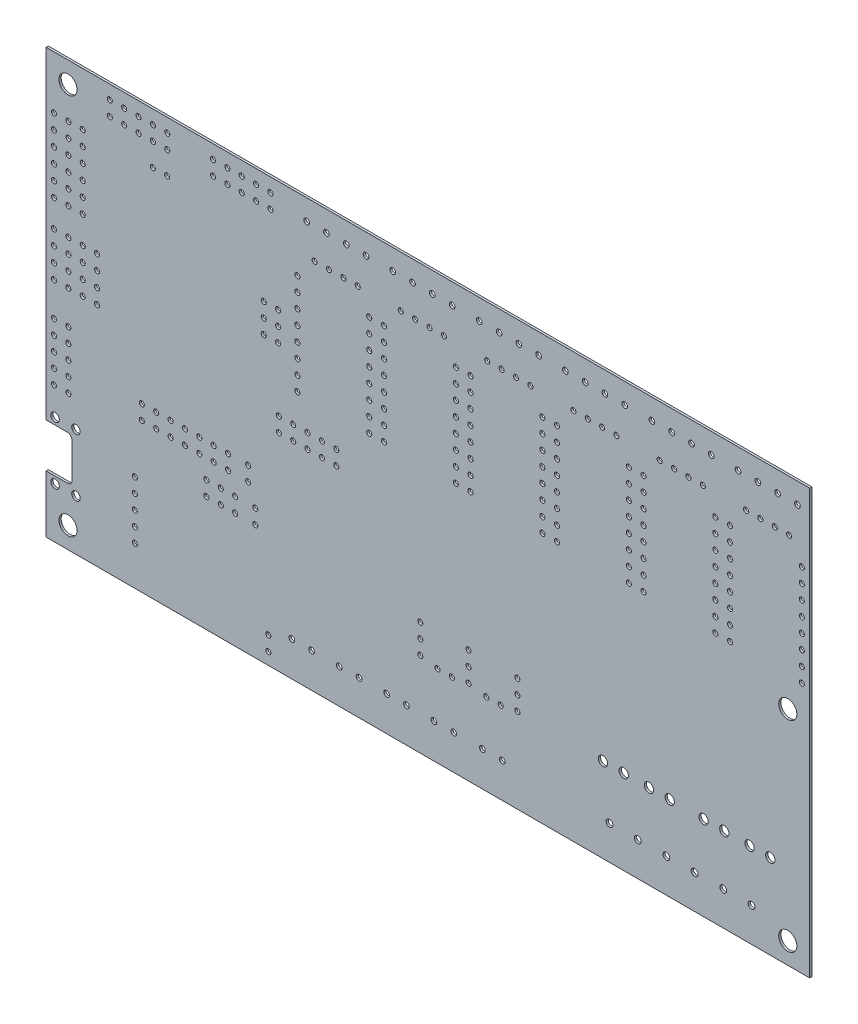
SolidWorks part; units mm, degrees
note: '?' marks a value the reader was unsure of.
ref_plane "Front Plane" through (0, 0, 0) normal (0, 0, 1) x (1, 0, 0)
ref_plane "Top Plane" through (0, 0, 0) normal (0, 1, 0) x (1, 0, 0)
ref_plane "Right Plane" through (0, 0, 0) normal (1, 0, 0) x (0, 0, -1)
ref_axis "x axis" through (-6.75, 0, 0) along (1, 0, 0)?
ref_axis "y axis" through (0, 78.75, 0) along (0, -1, 0)?
ref_axis "z axis" through (0, 0, -0.4107) along (0, 0, 1)?
sketch "Sketch1" plane through (0, 0, 0) normal (0, 0, 1) x (1, 0, 0)
  line L4 (135, 75) -> (0, 75)
  line L5 (0, 75) -> (0, 0)
  line L6 (0, 0) -> (135, 0)
  line L7 (135, 0) -> (135, 75)
extrude "Board" add sketch "Sketch1" along normal blind 0.3912
sketch "Sketch2" plane through (0, 0, 0.3912) normal (0, 0, 1) x (1, 0, 0)
  circle A0 centre (131.125, 39.25) radius 1.6
extrude "Cut-Extrude1" cut sketch "Sketch2" against normal blind 0.3912
sketch "Sketch3" plane through (0, 0, 0.3912) normal (0, 0, 1) x (1, 0, 0)
  circle A0 centre (131.125, 3.75) radius 1.6
extrude "Cut-Extrude2" cut sketch "Sketch3" against normal through all
sketch "Sketch4" plane through (0, 0, 0.3912) normal (0, 0, 1) x (1, 0, 0)
  circle A0 centre (3.875, 3.75) radius 1.6
extrude "Cut-Extrude3" cut sketch "Sketch4" against normal through all
sketch "Sketch5" plane through (0, 0, 0.3912) normal (0, 0, 1) x (1, 0, 0)
  circle A0 centre (3.875, 71.25) radius 1.6
extrude "Cut-Extrude4" cut sketch "Sketch5" against normal through all
sketch "Sketch6" plane through (0, 0, 0.3912) normal (0, 0, 1) x (1, 0, 0)
  line L0 (3.7788, 10.1428) -> (-0.0178, 10.1428)
  line L1 (-0.0178, 10.1428) -> (-0.0178, 17.9428)
  line L2 (-0.0178, 17.9428) -> (3.7788, 17.9428)
  line L3 (4.5788, 17.1428) -> (4.5788, 10.9428)
  arc A0 (3.7788, 17.9428) -> (4.5788, 17.1428) centre (3.7788, 17.1428) cw
  arc A1 (4.5788, 10.9428) -> (3.7788, 10.1428) centre (3.7787, 10.9428) cw
extrude "Cutout - Cutout 1" cut sketch "Sketch6" against normal blind 0.3912
sketch "Sketch7" plane through (0, 0, 0.3912) normal (0, 0, 1) x (1, 0, 0)
  circle A0 centre (87.0811, 71.3713) radius 0.5
  circle A1 centre (83.581, 71.3713) radius 0.5
  circle A2 centre (80.0811, 71.3713) radius 0.5
  circle A3 centre (76.5811, 71.3713) radius 0.5
  circle A4 centre (71.7826, 71.3713) radius 0.5
  circle A5 centre (68.2825, 71.3713) radius 0.5
  circle A6 centre (64.7826, 71.3713) radius 0.5
  circle A7 centre (61.2826, 71.3713) radius 0.5
  circle A8 centre (56.5639, 71.3713) radius 0.5
  circle A9 centre (53.0639, 71.3713) radius 0.5
  circle A10 centre (49.5639, 71.3713) radius 0.5
  circle A11 centre (46.0639, 71.3713) radius 0.5
  circle A12 centre (132.8313, 71.3713) radius 0.5
  circle A13 centre (129.3313, 71.3713) radius 0.5
  circle A14 centre (125.8314, 71.3713) radius 0.5
  circle A15 centre (122.3314, 71.3713) radius 0.5
  circle A16 centre (117.5998, 71.3713) radius 0.5
  circle A17 centre (114.0997, 71.3713) radius 0.5
  circle A18 centre (110.5998, 71.3713) radius 0.5
  circle A19 centre (107.0998, 71.3713) radius 0.5
  circle A20 centre (102.3031, 71.3713) radius 0.5
  circle A21 centre (98.8031, 71.3713) radius 0.5
  circle A22 centre (95.3031, 71.3713) radius 0.5
  circle A23 centre (91.8031, 71.3713) radius 0.5
  circle A24 centre (1.3965, 63.0504) radius 0.45
  circle A25 centre (3.9365, 63.0504) radius 0.45
  circle A26 centre (6.4765, 63.0504) radius 0.45
  circle A27 centre (1.3965, 65.6412) radius 0.45
  circle A28 centre (3.9365, 65.6412) radius 0.45
  circle A29 centre (6.4765, 65.6412) radius 0.45
  circle A30 centre (1.3965, 57.8688) radius 0.45
  circle A31 centre (3.9365, 57.8688) radius 0.45
  circle A32 centre (6.4765, 57.8688) radius 0.45
  circle A33 centre (1.3965, 60.4596) radius 0.45
  circle A34 centre (3.9365, 60.4596) radius 0.45
  circle A35 centre (6.4765, 60.4596) radius 0.45
  circle A36 centre (1.3965, 52.6872) radius 0.45
  circle A37 centre (3.9365, 52.6872) radius 0.45
  circle A38 centre (6.4765, 52.6872) radius 0.45
  circle A39 centre (1.3965, 55.278) radius 0.45
  circle A40 centre (3.9365, 55.278) radius 0.45
  circle A41 centre (6.4765, 55.278) radius 0.45
  circle A42 centre (66.1564, 20.0653) radius 0.45
  circle A43 centre (66.1564, 17.5253) radius 0.45
  circle A44 centre (66.1564, 14.9853) radius 0.45
  circle A45 centre (74.6883, 20.0653) radius 0.45
  circle A46 centre (74.6883, 17.5253) radius 0.45
  circle A47 centre (74.6883, 14.9853) radius 0.45
  circle A48 centre (83.3234, 20.0653) radius 0.45
  circle A49 centre (83.3234, 17.5253) radius 0.45
  circle A50 centre (83.3234, 14.9853) radius 0.45
  circle A51 centre (3.9363, 24.0045) radius 0.45
  circle A52 centre (1.3963, 24.0045) radius 0.45
  circle A53 centre (3.9363, 26.5445) radius 0.45
  circle A54 centre (1.3963, 26.5445) radius 0.45
  circle A55 centre (3.9363, 29.0845) radius 0.45
  circle A56 centre (1.3963, 29.0845) radius 0.45
  circle A57 centre (3.9363, 31.6245) radius 0.45
  circle A58 centre (1.3963, 31.6245) radius 0.45
  circle A59 centre (3.9363, 34.1645) radius 0.45
  circle A60 centre (1.3963, 34.1645) radius 0.45
  circle A61 centre (11.2672, 70.0327) radius 0.45
  circle A62 centre (11.2672, 72.5727) radius 0.45
  circle A63 centre (13.8072, 70.0327) radius 0.45
  circle A64 centre (13.8072, 72.5727) radius 0.45
  circle A65 centre (16.3472, 70.0327) radius 0.45
  circle A66 centre (16.3472, 72.5727) radius 0.45
  circle A67 centre (18.8872, 70.0327) radius 0.45
  circle A68 centre (18.8872, 72.5727) radius 0.45
  circle A69 centre (21.4272, 70.0327) radius 0.45
  circle A70 centre (21.4272, 72.5727) radius 0.45
  circle A71 centre (29.5086, 70.0327) radius 0.45
  circle A72 centre (29.5086, 72.5727) radius 0.45
  circle A73 centre (32.0486, 70.0327) radius 0.45
  circle A74 centre (32.0486, 72.5727) radius 0.45
  circle A75 centre (34.5886, 70.0327) radius 0.45
  circle A76 centre (34.5886, 72.5727) radius 0.45
  circle A77 centre (37.1286, 70.0327) radius 0.45
  circle A78 centre (37.1286, 72.5727) radius 0.45
  circle A79 centre (39.6686, 70.0327) radius 0.45
  circle A80 centre (39.6686, 72.5727) radius 0.45
  circle A81 centre (41.1521, 36.5667) radius 0.45
  circle A82 centre (41.1521, 39.1067) radius 0.45
  circle A83 centre (43.6921, 36.5667) radius 0.45
  circle A84 centre (43.6921, 39.1067) radius 0.45
  circle A85 centre (46.2321, 36.5667) radius 0.45
  circle A86 centre (46.2321, 39.1067) radius 0.45
  circle A87 centre (48.7721, 36.5667) radius 0.45
  circle A88 centre (48.7721, 39.1067) radius 0.45
  circle A89 centre (51.3121, 36.5667) radius 0.45
  circle A90 centre (51.3121, 39.1067) radius 0.45
  circle A91 centre (1.3965, 47.8881) radius 0.45
  circle A92 centre (3.9365, 47.8881) radius 0.45
  circle A93 centre (6.4765, 47.8881) radius 0.45
  circle A94 centre (9.0165, 47.8881) radius 0.45
  circle A95 centre (1.3965, 45.2971) radius 0.45
  circle A96 centre (3.9365, 45.2971) radius 0.45
  circle A97 centre (6.4765, 45.2971) radius 0.45
  circle A98 centre (9.0165, 45.2971) radius 0.45
  circle A99 centre (1.3965, 42.7061) radius 0.45
  circle A100 centre (3.9365, 42.7061) radius 0.45
  circle A101 centre (6.4765, 42.7061) radius 0.45
  circle A102 centre (9.0165, 42.7061) radius 0.45
  circle A103 centre (1.3965, 40.1151) radius 0.45
  circle A104 centre (3.9365, 40.1151) radius 0.45
  circle A105 centre (6.4765, 40.1151) radius 0.45
  circle A106 centre (9.0165, 40.1151) radius 0.45
  circle A107 centre (100.847, 65.9861) radius 0.45
  circle A108 centre (98.307, 65.9861) radius 0.45
  circle A109 centre (95.767, 65.9861) radius 0.45
  circle A110 centre (93.227, 65.9861) radius 0.45
  circle A111 centre (116.1001, 65.9861) radius 0.45
  circle A112 centre (113.5601, 65.9861) radius 0.45
  circle A113 centre (111.0201, 65.9861) radius 0.45
  circle A114 centre (108.4801, 65.9861) radius 0.45
  circle A115 centre (131.3611, 65.9861) radius 0.45
  circle A116 centre (128.8211, 65.9861) radius 0.45
  circle A117 centre (126.2811, 65.9861) radius 0.45
  circle A118 centre (123.7411, 65.9861) radius 0.45
  circle A119 centre (55.0987, 65.9861) radius 0.45
  circle A120 centre (52.5587, 65.9861) radius 0.45
  circle A121 centre (50.0187, 65.9861) radius 0.45
  circle A122 centre (47.4787, 65.9861) radius 0.45
  circle A123 centre (70.3205, 65.9861) radius 0.45
  circle A124 centre (67.7805, 65.9861) radius 0.45
  circle A125 centre (65.2405, 65.9861) radius 0.45
  circle A126 centre (62.7005, 65.9861) radius 0.45
  circle A127 centre (85.6143, 65.9861) radius 0.45
  circle A128 centre (83.0743, 65.9861) radius 0.45
  circle A129 centre (80.5343, 65.9861) radius 0.45
  circle A130 centre (77.9943, 65.9861) radius 0.45
  circle A131 centre (16.9301, 26.329) radius 0.45
  circle A132 centre (16.9301, 28.8691) radius 0.45
  circle A133 centre (19.4701, 26.329) radius 0.45
  circle A134 centre (19.4701, 28.8691) radius 0.45
  circle A135 centre (22.0101, 26.329) radius 0.45
  circle A136 centre (22.0101, 28.8691) radius 0.45
  circle A137 centre (24.5501, 26.329) radius 0.45
  circle A138 centre (24.5501, 28.8691) radius 0.45
  circle A139 centre (27.0901, 26.329) radius 0.45
  circle A140 centre (27.0901, 28.8691) radius 0.45
  circle A141 centre (29.6301, 26.329) radius 0.45
  circle A142 centre (29.6301, 28.8691) radius 0.45
  circle A143 centre (32.1701, 26.329) radius 0.45
  circle A144 centre (32.1701, 28.8691) radius 0.45
  circle A145 centre (41.0197, 50.2441) radius 0.45
  circle A146 centre (38.4797, 50.2441) radius 0.45
  circle A147 centre (41.0197, 52.7841) radius 0.45
  circle A148 centre (38.4797, 52.7841) radius 0.45
  circle A149 centre (41.0197, 55.3241) radius 0.45
  circle A150 centre (38.4797, 55.3241) radius 0.45
  circle A151 centre (33.4218, 22.934) radius 0.45
  circle A152 centre (33.4218, 20.394) radius 0.45
  circle A153 centre (30.8818, 22.934) radius 0.45
  circle A154 centre (30.8818, 20.394) radius 0.45
  circle A155 centre (28.3418, 22.934) radius 0.45
  circle A156 centre (28.3418, 20.394) radius 0.45
  circle A157 centre (21.4107, 66.0154) radius 0.45
  circle A158 centre (18.8707, 66.0154) radius 0.45
  circle A159 centre (69.1994, 14.4531) radius 0.45
  circle A160 centre (71.7394, 14.4531) radius 0.45
  circle A161 centre (77.836, 14.4531) radius 0.45
  circle A162 centre (80.376, 14.4531) radius 0.45
  circle A163 centre (36.9854, 22.934) radius 0.45
  circle A164 centre (36.9854, 20.394) radius 0.45
  circle A165 centre (35.726, 28.8689) radius 0.45
  circle A166 centre (35.726, 26.3289) radius 0.45
  circle A167 centre (39.2894, 4.6759) radius 0.45
  circle A168 centre (39.2894, 2.1359) radius 0.45
  circle A169 centre (103.0267, 52.0859) radius 0.45
  circle A170 centre (103.0267, 49.5459) radius 0.45
  circle A171 centre (103.0267, 54.6259) radius 0.45
  circle A172 centre (103.0267, 57.1659) radius 0.45
  circle A173 centre (90.3267, 44.4659) radius 0.45
  circle A174 centre (90.3267, 62.2459) radius 0.45
  circle A175 centre (103.0267, 44.4659) radius 0.45
  circle A176 centre (103.0267, 59.7059) radius 0.45
  circle A177 centre (90.3267, 59.7059) radius 0.45
  circle A178 centre (90.3267, 57.1659) radius 0.45
  circle A179 centre (90.3267, 54.6259) radius 0.45
  circle A180 centre (90.3267, 52.0859) radius 0.45
  circle A181 centre (90.3267, 49.5459) radius 0.45
  circle A182 centre (90.3267, 47.0059) radius 0.45
  circle A183 centre (103.0267, 47.0059) radius 0.45
  circle A184 centre (103.0267, 62.2459) radius 0.45
  circle A185 centre (118.3179, 52.0859) radius 0.45
  circle A186 centre (118.3179, 49.5459) radius 0.45
  circle A187 centre (118.3179, 54.6259) radius 0.45
  circle A188 centre (118.3179, 57.1659) radius 0.45
  circle A189 centre (105.6179, 44.4659) radius 0.45
  circle A190 centre (105.6179, 62.2459) radius 0.45
  circle A191 centre (118.3179, 44.4659) radius 0.45
  circle A192 centre (118.3179, 59.7059) radius 0.45
  circle A193 centre (105.6179, 59.7059) radius 0.45
  circle A194 centre (105.6179, 57.1659) radius 0.45
  circle A195 centre (105.6179, 54.6259) radius 0.45
  circle A196 centre (105.6179, 52.0859) radius 0.45
  circle A197 centre (105.6179, 49.5459) radius 0.45
  circle A198 centre (105.6179, 47.0059) radius 0.45
  circle A199 centre (118.3179, 47.0059) radius 0.45
  circle A200 centre (118.3179, 62.2459) radius 0.45
  circle A201 centre (133.6141, 52.0859) radius 0.45
  circle A202 centre (133.6141, 49.5459) radius 0.45
  circle A203 centre (133.6141, 54.6259) radius 0.45
  circle A204 centre (133.6141, 57.1659) radius 0.45
  circle A205 centre (120.9141, 44.4659) radius 0.45
  circle A206 centre (120.9141, 62.2459) radius 0.45
  circle A207 centre (133.6141, 44.4659) radius 0.45
  circle A208 centre (133.6141, 59.7059) radius 0.45
  circle A209 centre (120.9141, 59.7059) radius 0.45
  circle A210 centre (120.9141, 57.1659) radius 0.45
  circle A211 centre (120.9141, 54.6259) radius 0.45
  circle A212 centre (120.9141, 52.0859) radius 0.45
  circle A213 centre (120.9141, 49.5459) radius 0.45
  circle A214 centre (120.9141, 47.0059) radius 0.45
  circle A215 centre (133.6141, 47.0059) radius 0.45
  circle A216 centre (133.6141, 62.2459) radius 0.45
  circle A217 centre (57.1311, 52.0859) radius 0.45
  circle A218 centre (57.1311, 49.5459) radius 0.45
  circle A219 centre (57.1311, 54.6259) radius 0.45
  circle A220 centre (57.1311, 57.1659) radius 0.45
  circle A221 centre (44.4311, 44.4659) radius 0.45
  circle A222 centre (44.4311, 62.2459) radius 0.45
  circle A223 centre (57.1311, 44.4659) radius 0.45
  circle A224 centre (57.1311, 59.7059) radius 0.45
  circle A225 centre (44.4311, 59.7059) radius 0.45
  circle A226 centre (44.4311, 57.1659) radius 0.45
  circle A227 centre (44.4311, 54.6259) radius 0.45
  circle A228 centre (44.4311, 52.0859) radius 0.45
  circle A229 centre (44.4311, 49.5459) radius 0.45
  circle A230 centre (44.4311, 47.0059) radius 0.45
  circle A231 centre (57.1311, 47.0059) radius 0.45
  circle A232 centre (57.1311, 62.2459) radius 0.45
  circle A233 centre (72.4458, 52.0859) radius 0.45
  circle A234 centre (72.4458, 49.5459) radius 0.45
  circle A235 centre (72.4458, 54.6259) radius 0.45
  circle A236 centre (72.4458, 57.1659) radius 0.45
  circle A237 centre (59.7458, 44.4659) radius 0.45
  circle A238 centre (59.7458, 62.2459) radius 0.45
  circle A239 centre (72.4458, 44.4659) radius 0.45
  circle A240 centre (72.4458, 59.7059) radius 0.45
  circle A241 centre (59.7458, 59.7059) radius 0.45
  circle A242 centre (59.7458, 57.1659) radius 0.45
  circle A243 centre (59.7458, 54.6259) radius 0.45
  circle A244 centre (59.7458, 52.0859) radius 0.45
  circle A245 centre (59.7458, 49.5459) radius 0.45
  circle A246 centre (59.7458, 47.0059) radius 0.45
  circle A247 centre (72.4458, 47.0059) radius 0.45
  circle A248 centre (72.4458, 62.2459) radius 0.45
  circle A249 centre (87.7344, 52.0859) radius 0.45
  circle A250 centre (87.7344, 49.5459) radius 0.45
  circle A251 centre (87.7344, 54.6259) radius 0.45
  circle A252 centre (87.7344, 57.1659) radius 0.45
  circle A253 centre (75.0345, 44.4659) radius 0.45
  circle A254 centre (75.0345, 62.2459) radius 0.45
  circle A255 centre (87.7344, 44.4659) radius 0.45
  circle A256 centre (87.7344, 59.7059) radius 0.45
  circle A257 centre (75.0345, 59.7059) radius 0.45
  circle A258 centre (75.0345, 57.1659) radius 0.45
  circle A259 centre (75.0345, 54.6259) radius 0.45
  circle A260 centre (75.0345, 52.0859) radius 0.45
  circle A261 centre (75.0345, 49.5459) radius 0.45
  circle A262 centre (75.0345, 47.0059) radius 0.45
  circle A263 centre (87.7344, 47.0059) radius 0.45
  circle A264 centre (87.7344, 62.2459) radius 0.45
  circle A265 centre (46.9445, 6.1219) radius 0.5
  circle A266 centre (43.4445, 6.1219) radius 0.5
  circle A267 centre (55.324, 6.1219) radius 0.5
  circle A268 centre (51.824, 6.1219) radius 0.5
  circle A269 centre (63.7062, 6.1219) radius 0.5
  circle A270 centre (60.2062, 6.1219) radius 0.5
  circle A271 centre (72.0695, 6.1219) radius 0.5
  circle A272 centre (68.5695, 6.1219) radius 0.5
  circle A273 centre (80.6341, 6.1219) radius 0.5
  circle A274 centre (77.1341, 6.1219) radius 0.5
  circle A275 centre (124.7136, 5.9848) radius 0.6
  circle A276 centre (119.7136, 5.9848) radius 0.6
  circle A277 centre (114.6574, 5.9848) radius 0.6
  circle A278 centre (109.6574, 5.9848) radius 0.6
  circle A279 centre (104.5996, 5.9848) radius 0.6
  circle A280 centre (99.5996, 5.9848) radius 0.6
  circle A281 centre (5.2822, 19.1428) radius 0.75
  circle A282 centre (5.2822, 8.9428) radius 0.75
  circle A283 centre (1.5822, 8.9428) radius 0.75
  circle A284 centre (1.5822, 19.1428) radius 0.75
  circle A285 centre (15.688, 6.9074) radius 0.45
  circle A286 centre (15.688, 9.4474) radius 0.45
  circle A287 centre (15.688, 11.9874) radius 0.45
  circle A288 centre (15.688, 14.5274) radius 0.45
  circle A289 centre (15.688, 17.0674) radius 0.45
  circle A290 centre (128.032, 14.9475) radius 0.825
  circle A291 centre (124.372, 14.9475) radius 0.825
  circle A292 centre (119.902, 14.9475) radius 0.825
  circle A293 centre (116.242, 14.9475) radius 0.825
  circle A294 centre (102.1174, 14.9474) radius 0.825
  circle A295 centre (98.4574, 14.9474) radius 0.825
  circle A296 centre (110.2474, 14.9474) radius 0.825
  circle A297 centre (106.5874, 14.9474) radius 0.825
extrude "Cut-Extrude6" cut sketch "Sketch7" against normal through all
